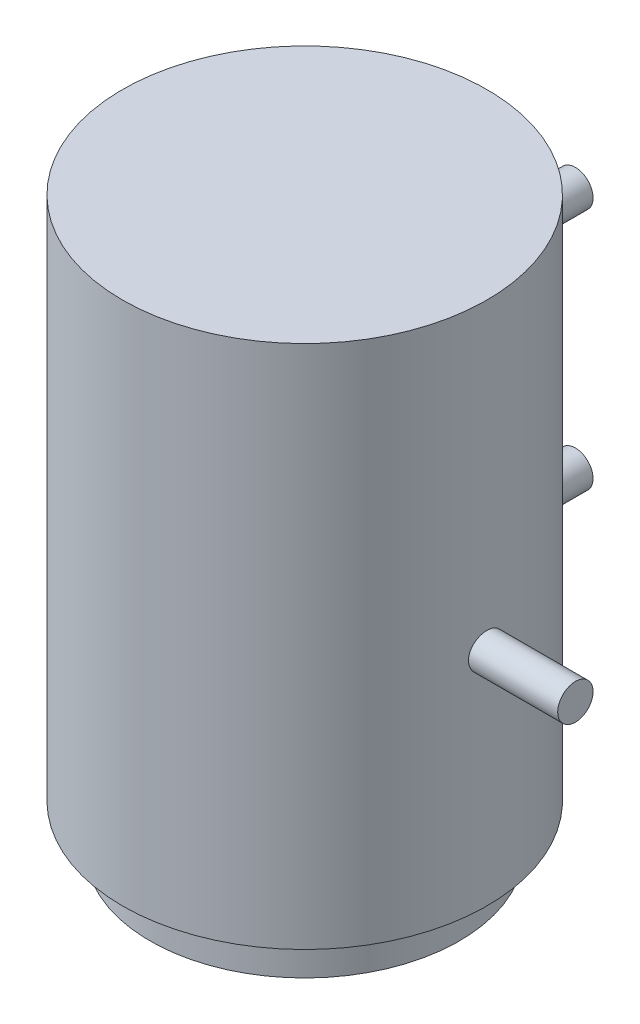
SolidWorks part; units mm, degrees
note: '?' marks a value the reader was unsure of.
ref_plane "Front Plane" through (0, 0, 0) normal (0, 0, 1) x (1, 0, 0)
ref_plane "Top Plane" through (0, 0, 0) normal (0, 1, 0) x (1, 0, 0)
ref_plane "Right Plane" through (0, 0, 0) normal (1, 0, 0) x (0, 0, -1)
sketch "Sketch1" plane through (0, 0, 0) normal (0, 1, 0) x (1, 0, 0)
  circle A0 centre (0, 0) radius 16.5
  dimension "D1" = 33
extrude "Boss-Extrude1" add sketch "Sketch1" along normal blind 47.5
sketch "Sketch2" plane through (0, 0, 0) normal (0, -1, 0) x (1, 0, 0)
  circle A0 centre (0, 0) radius 14
  dimension "D1" = 28
extrude "Boss-Extrude2" add sketch "Sketch2" along normal blind 4
ref_point "Point2"
ref_axis "Axis1" through (0, 0, 0) along (0, 0, -1)?
ref_plane "Plane1" through (0, 0, -16.5) normal (0, 0, -1) x (-1, 0, 0)
sketch "Sketch4" plane through (0, 0, -16.5) normal (0, 0, -1) x (-1, 0, 0)
  line L0 (0, 0) -> (0, 47.6435) construction
  line L1 (-16.5, 0) -> (16.5, 0) construction
  circle A0 centre (0, 35.8005) radius 1.6
  circle A1 centre (0, 13.8005) radius 1.6
  point P9 (0, 0)
  point P10 (0, 26.9948)
  point P11 (0, 0)
  dimension "D3" = 3.2
  dimension "D1" = 13.8005
  dimension "D2" = 22
extrude "Boss-Extrude3" add sketch "Sketch4" against normal blind 1 and the other way blind 8
ref_plane "Plane2" through (16.5, 0, 0) normal (1, 0, 0) x (0, 0, -1)
sketch "Sketch5" plane through (16.5, 0, 0) normal (1, 0, 0) x (0, 0, -1)
  line L0 (0, 0) -> (0, 47.5933) construction
  circle A0 centre (0, 20) radius 1.6
  dimension "D1" = 3.2
  dimension "D2" = 20
extrude "Boss-Extrude4" add sketch "Sketch5" against normal blind 1 and the other way blind 8
